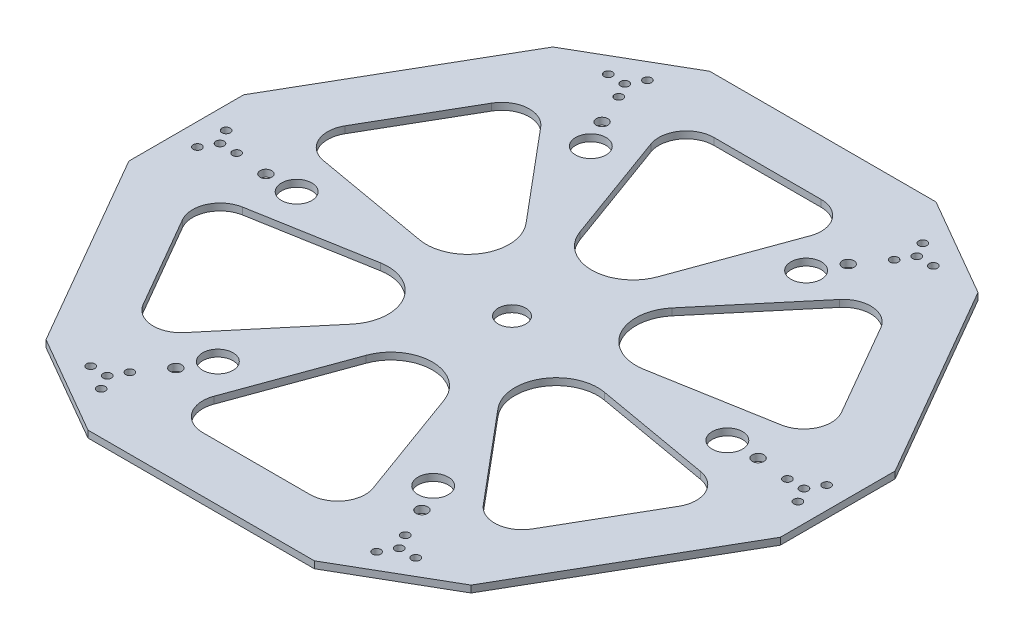
SolidWorks part; units mm, degrees
ref_plane "前视基准面" through (0, 0, 0) normal (0, 0, 1) x (1, 0, 0)
ref_plane "上视基准面" through (0, 0, 0) normal (0, 1, 0) x (1, 0, 0)
ref_plane "右视基准面" through (0, 0, 0) normal (1, 0, 0) x (0, 0, -1)
other "Configuration Table"
sketch "草图2" plane through (0, 0, 0) normal (0, 1, 0) x (1, 0, 0)
  line L1 (45, 0) -> (22.5, 38.9711)
  line L2 (22.5, 38.9711) -> (-22.5, 38.9711)
  line L3 (-22.5, 38.9711) -> (-45, 0)
  line L4 (-45, 0) -> (-22.5, -38.9711)
  line L5 (-22.5, -38.9711) -> (22.5, -38.9711)
  line L6 (22.5, -38.9711) -> (45, 0)
  line L7 (-54.5, 0) -> (-27.25, -47.1984)
  line L8 (-27.25, -47.1984) -> (27.25, -47.1984)
  line L9 (27.25, -47.1984) -> (54.5, 0)
  line L10 (54.5, 0) -> (27.25, 47.1984)
  line L11 (27.25, 47.1984) -> (-27.25, 47.1984)
  line L12 (-27.25, 47.1984) -> (-54.5, 0)
  circle A0 centre (0, 0) radius 38.9711 construction
  circle A1 centre (0, 0) radius 47.1984 construction
  circle A2 centre (0, 0) radius 5
  dimension "D3" = 10
  dimension "D1" = 45
  dimension "D2" = 9.5
extrude "凸台-拉伸1" add sketch "草图2" along normal blind 2.5 contours L5 L6 L1 L2 L3 L4 | L11 L12 L7 L8 L9 L10 L6 L5 L4 L3 L2 L1 region at (32.7189, 0, 18.8903) region at (-39.6262, 0, -22.8782)
sketch "草图3" plane through (0, 2.5, 0) normal (0, 1, 0) x (1, 0, 0)
  line L7 (-45, 0) -> (-22.5, -38.9711) construction
  line L8 (-22.5, -38.9711) -> (22.5, -38.9711) construction
  line L9 (22.5, -38.9711) -> (45, 0) construction
  line L10 (45, 0) -> (22.5, 38.9711) construction
  line L11 (22.5, 38.9711) -> (-22.5, 38.9711) construction
  line L12 (-22.5, 38.9711) -> (-45, 0) construction
  circle A0 centre (0, 0) radius 38.9711 construction
  circle A7 centre (-22.5, 38.9711) radius 2.1
  circle A8 centre (22.5, 38.9711) radius 2.1
  circle A9 centre (45, 0) radius 2.1
  circle A10 centre (22.5, -38.9711) radius 2.1
  circle A11 centre (-22.5, -38.9711) radius 2.1
  circle A12 centre (-45, 0) radius 2.1
  point P23 (0, 0)
  point P24 (0, 0)
  dimension "D2" = 4.2
  dimension "D1" = 45
  dimension "D3" = 6
extrude "切除-拉伸1" [suppressed] cut sketch "草图3" against normal blind 2.5
sketch "草图4" plane through (0, 2.5, 0) normal (0, 1, 0) x (1, 0, 0)
  line L0 (-27.25, 47.1984) -> (-54.5, 0) construction
  line L1 (-54.5, 0) -> (-27.25, -47.1984)
  line L2 (-27.25, -47.1984) -> (27.25, -47.1984)
  line L3 (27.25, -47.1984) -> (54.5, 0)
  line L4 (54.5, 0) -> (27.25, 47.1984)
  line L5 (27.25, 47.1984) -> (-27.25, 47.1984)
  line L6 (-27.25, 47.1984) -> (-54.5, 0)
  line L7 (-100.688, 0) -> (-50.344, -87.1984)
  line L8 (-50.344, -87.1984) -> (50.344, -87.1984)
  line L9 (50.344, -87.1984) -> (100.688, 0)
  line L10 (100.688, 0) -> (50.344, 87.1984)
  line L11 (50.344, 87.1984) -> (-50.344, 87.1984)
  line L12 (-50.344, 87.1984) -> (-100.688, 0)
  circle A0 centre (0, 0) radius 47.1984 construction
  circle A1 centre (0, 0) radius 87.1984 construction
  dimension "D1" = 40
extrude "凸台-拉伸2" add sketch "草图4" against normal up to surface (2.5 mm away) up to face at (0, 0, 5)
sketch "草图5" plane through (0, 2.5, 0) normal (0, 1, 0) x (1, 0, 0)
  line L0 (-50.344, 87.1984) -> (-100.688, 0) construction
  line L1 (-89.141, 0) -> (-44.5705, -77.1984) construction
  line L2 (-44.5705, -77.1984) -> (44.5705, -77.1984) construction
  line L3 (44.5705, -77.1984) -> (89.141, 0) construction
  line L4 (89.141, 0) -> (44.5705, 77.1984) construction
  line L5 (44.5705, 77.1984) -> (-44.5705, 77.1984) construction
  line L6 (-44.5705, 77.1984) -> (-89.141, 0) construction
  circle A0 centre (0, 0) radius 77.1984 construction
  circle A1 centre (-44.5705, 77.1984) radius 2.1
  circle A2 centre (44.5705, 77.1984) radius 2.1
  circle A3 centre (89.141, 0) radius 2.1
  circle A4 centre (44.5705, -77.1984) radius 2.1
  circle A5 centre (-44.5705, -77.1984) radius 2.1
  circle A6 centre (-89.141, 0) radius 2.1
  point P24 (0, 0)
  dimension "D2" = 4.2
  dimension "D1" = 10
  dimension "D3" = 6
extrude "切除-拉伸2" cut sketch "草图5" against normal blind 10
sketch "草图8" plane through (0, 2.5, 0) normal (0, 1, 0) x (1, 0, 0)
  line L0 (50.344, 87.1984) -> (-50.344, 87.1984) construction
  line L1 (-100.688, 0) -> (-50.344, -87.1984) construction
  circle A0 centre (-44.5705, 77.1984) radius 10
  circle A1 centre (44.5705, 77.1984) radius 10
  circle A2 centre (89.141, 0) radius 10
  circle A3 centre (44.5705, -77.1984) radius 10
  circle A4 centre (-44.5705, -77.1984) radius 10
  circle A5 centre (-89.141, 0) radius 10
  circle A6 centre (-113.6008, 65.5875) radius 60
  circle A7 centre (0, 131.175) radius 60
  circle A8 centre (113.6008, 65.5875) radius 60
  circle A9 centre (113.6008, -65.5875) radius 60
  circle A10 centre (0, -131.175) radius 60
  circle A11 centre (-113.6008, -65.5875) radius 60
  point P36 (0, 0)
  line M23 (-50.344, 87.1984) -> (-100.688, 0)
  line M24 (-100.688, 0) -> (-50.344, -87.1984)
  line M25 (-50.344, -87.1984) -> (50.344, -87.1984)
  line M26 (50.344, -87.1984) -> (100.688, 0)
  line M27 (100.688, 0) -> (50.344, 87.1984)
  line M28 (50.344, 87.1984) -> (-50.344, 87.1984)
  dimension "D1" = 120
  dimension "D2" = 6
extrude "切除-拉伸3" cut sketch "草图8" against normal blind 10 contours A0 M28 M23 | A7 A0 M28 | A6 A0 M23 | A7 M28 | A8 M27 | A9 M26 | A10 M25 | A11 M24 | A6 M23 | A1 M27 M28 | A7 A1 M28 | A8 A1 M27 | A8 A2 M27 | A2 M26 M27 | A9 A2 M26 | A9 A3 M26 | A10 A3 M25 | A3 M25 M26 | A11 A4 M24 | A4 M24 M25 | A10 A4 M25 | A5 M23 M24 | A6 A5 M23 | A11 A5 M24 | A6 region at (-41.0716, 2.5, -86.7224) region at (0, 2.5, -80.7095) region at (-54.568, 2.5, -78.9302) region at (-69.8965, 2.5, -40.3547) region at (-49.7383, 2.5, -86.1493) region at (41.0716, 2.5, -86.7224) region at (49.7383, 2.5, -86.1493) region at (54.568, 2.5, -78.9302) region at (69.8965, 2.5, -40.3547) region at (-95.6395, 2.5, -7.7922) region at (95.6395, 2.5, -7.7922) region at (-99.4766, 2.5, 0) region at (99.4766, 2.5, 0) region at (95.6395, 2.5, 7.7922) region at (69.8965, 2.5, 40.3547) region at (-95.6395, 2.5, 7.7922) region at (-69.8965, 2.5, 40.3547) region at (54.568, 2.5, 78.9302) region at (41.0716, 2.5, 86.7224) region at (0, 2.5, 80.7095) region at (-54.568, 2.5, 78.9302) region at (49.7383, 2.5, 86.1493) region at (-41.0716, 2.5, 86.7224) region at (-49.7383, 2.5, 86.1493)
sketch "草图10" plane through (0, 2.5, 0) normal (0, 1, 0) x (1, 0, 0)
  line L0 (-123, 12.1244) -> (-123, -12.1244)
  line L1 (-130, 0) -> (-65, -112.5833)
  line L2 (-65, -112.5833) -> (65, -112.5833)
  line L3 (65, -112.5833) -> (130, 0)
  line L4 (130, 0) -> (65, 112.5833)
  line L5 (65, 112.5833) -> (-65, 112.5833)
  line L6 (-65, 112.5833) -> (-130, 0)
  line L7 (-51, 112.5833) -> (-72, 100.4589)
  line L8 (72, 100.4589) -> (51, 112.5833)
  line L9 (123, -12.1244) -> (123, 12.1244)
  line L10 (51, -112.5833) -> (72, -100.4589)
  line L11 (-72, -100.4589) -> (-51, -112.5833)
  circle A0 centre (0, 0) radius 112.5833 construction
  arc A3 (-38.2033, 84.9093) -> (38.2033, 84.9093) centre (0, 131.175) ccw
  arc A5 (-38.2033, 84.9093) -> (38.2033, 84.9093) centre (0, 131.175) ccw
  arc A17 (-38.2033, 84.9093) -> (-54.432, 75.5397) centre (-44.5705, 77.1984) ccw
  arc A18 (-38.2033, 84.9093) -> (-54.432, 75.5397) centre (-44.5705, 77.1984) ccw
  arc A19 (-92.6353, 9.3696) -> (-54.432, 75.5397) centre (-113.6008, 65.5875) ccw
  arc A20 (-92.6353, 9.3696) -> (-54.432, 75.5397) centre (-113.6008, 65.5875) ccw
  arc A21 (-92.6353, 9.3696) -> (-92.6353, -9.3696) centre (-89.141, 0) ccw
  arc A22 (-92.6353, 9.3696) -> (-92.6353, -9.3696) centre (-89.141, 0) ccw
  arc A23 (-54.432, -75.5397) -> (-92.6353, -9.3696) centre (-113.6008, -65.5875) ccw
  arc A36 (-54.432, -75.5397) -> (-92.6353, -9.3696) centre (-113.6008, -65.5875) ccw
  arc A37 (-54.432, -75.5397) -> (-38.2033, -84.9093) centre (-44.5705, -77.1984) ccw
  arc A38 (-54.432, -75.5397) -> (-38.2033, -84.9093) centre (-44.5705, -77.1984) ccw
  arc A39 (38.2033, -84.9093) -> (-38.2033, -84.9093) centre (0, -131.175) ccw
  arc A40 (38.2033, -84.9093) -> (-38.2033, -84.9093) centre (0, -131.175) ccw
  arc A41 (38.2033, -84.9093) -> (54.432, -75.5397) centre (44.5705, -77.1984) ccw
  arc A42 (38.2033, -84.9093) -> (54.432, -75.5397) centre (44.5705, -77.1984) ccw
  arc A43 (92.6353, -9.3696) -> (54.432, -75.5397) centre (113.6008, -65.5875) ccw
  arc A44 (92.6353, -9.3696) -> (54.432, -75.5397) centre (113.6008, -65.5875) ccw
  arc A45 (92.6353, -9.3696) -> (92.6353, 9.3696) centre (89.141, 0) ccw
  arc A46 (92.6353, -9.3696) -> (92.6353, 9.3696) centre (89.141, 0) ccw
  arc A47 (54.432, 75.5397) -> (92.6353, 9.3696) centre (113.6008, 65.5875) ccw
  arc A48 (54.432, 75.5397) -> (92.6353, 9.3696) centre (113.6008, 65.5875) ccw
  arc A49 (54.432, 75.5397) -> (38.2033, 84.9093) centre (44.5705, 77.1984) ccw
  arc A50 (54.432, 75.5397) -> (38.2033, 84.9093) centre (44.5705, 77.1984) ccw
  point P47 (0, 0)
  arc M32 (38.2033, 84.9093) -> (-38.2033, 84.9093) centre (0, 131.175) cw
  arc M33 (-38.2033, 84.9093) -> (-54.432, 75.5397) centre (-44.5705, 77.1984) ccw
  arc M34 (-54.432, 75.5397) -> (-92.6353, 9.3696) centre (-113.6008, 65.5875) cw
  arc M35 (-92.6353, 9.3696) -> (-92.6353, -9.3696) centre (-89.141, 0) ccw
  arc M36 (-92.6353, -9.3696) -> (-54.432, -75.5397) centre (-113.6008, -65.5875) cw
  arc M37 (-54.432, -75.5397) -> (-38.2033, -84.9093) centre (-44.5705, -77.1984) ccw
  arc M38 (-38.2033, -84.9093) -> (38.2033, -84.9093) centre (0, -131.175) cw
  arc M39 (38.2033, -84.9093) -> (54.432, -75.5397) centre (44.5705, -77.1984) ccw
  arc M40 (54.432, -75.5397) -> (92.6353, -9.3696) centre (113.6008, -65.5875) cw
  arc M41 (92.6353, -9.3696) -> (92.6353, 9.3696) centre (89.141, 0) ccw
  arc M42 (92.6353, 9.3696) -> (54.432, 75.5397) centre (113.6008, 65.5875) cw
  arc M43 (54.432, 75.5397) -> (38.2033, 84.9093) centre (44.5705, 77.1984) ccw
  dimension "D2" = 130
  dimension "D3" = 7
  dimension "D1" = 0
  dimension "D4" = 6
extrude "凸台-拉伸3" add sketch "草图10" against normal up to surface (2.5 mm away) contours L1 L11 L2 L10 L3 L9 L4 L8 L5 L7 L6 L0 M32 M43 M42 M41 M40 M39 M38 M37 M36 M35 M34 M33 region at (-94.6119, 2.5, -54.6242) up to face at (-89.141, 0, 2.1)
sketch "草图11" plane through (0, 2.5, 0) normal (0, 1, 0) x (1, 0, 0)
  line L0 (-123, 12.1244) -> (-123, -12.1244) construction
  line L1 (-123, 1.2426) -> (-107, 1.2426) construction
  line L2 (-107, 1.2426) -> (-101, 1.2426) construction
  circle A0 centre (-107, 1.2426) radius 1.5
  circle A1 centre (-101, 1.2426) radius 1.5
  circle A2 centre (-110, -3.9536) radius 1.5
  circle A3 centre (-110, 6.4387) radius 1.5
  point P12 (-107, 1.2426)
  dimension "D1" = 3
  dimension "D2" = 16
  dimension "D3" = 6
  dimension "D4" = 3
extrude "切除-拉伸4" cut sketch "草图11" against normal through all
pattern_circular "阵列(圆周)1" count 6 over 360 about axis through (0, 2.5, 0) along (0, 1, 0) of "切除-拉伸4"
sketch "草图12" plane through (0, 2.5, 0) normal (0, 1, 0) x (1, 0, 0)
  line L0 (0, 0) -> (60.8571, 0) construction
  line L1 (-118, 68.1273) -> (-118, -68.1273)
  line L2 (-118, -68.1273) -> (0, -136.2547)
  line L3 (0, -136.2547) -> (118, -68.1273)
  line L4 (118, -68.1273) -> (118, 68.1273)
  line L5 (118, 68.1273) -> (0, 136.2547)
  line L6 (0, 136.2547) -> (-118, 68.1273)
  line L7 (-51, 112.5833) -> (-72, 100.4589) construction
  line L9 (-145.896, 84.2331) -> (-145.896, -84.2331)
  line L10 (-145.896, -84.2331) -> (0, -168.4662)
  line L11 (0, -168.4662) -> (145.896, -84.2331)
  line L12 (145.896, -84.2331) -> (145.896, 84.2331)
  line L13 (145.896, 84.2331) -> (0, 168.4662)
  line L14 (0, 168.4662) -> (-145.896, 84.2331)
  circle A0 centre (0, 0) radius 118 construction
  circle A1 centre (0, 0) radius 145.896 construction
  line M51 (-123, -12.1244) -> (-72, -100.4589)
  line M52 (-72, -100.4589) -> (-51, -112.5833)
  line M53 (-51, -112.5833) -> (51, -112.5833)
  line M54 (51, -112.5833) -> (72, -100.4589)
  line M55 (72, -100.4589) -> (123, -12.1244)
  line M56 (123, -12.1244) -> (123, 12.1244)
  line M57 (123, 12.1244) -> (72, 100.4589)
  line M58 (72, 100.4589) -> (51, 112.5833)
  line M59 (51, 112.5833) -> (-51, 112.5833)
  line M60 (-51, 112.5833) -> (-72, 100.4589)
  line M61 (-72, 100.4589) -> (-123, 12.1244)
  line M62 (-123, 12.1244) -> (-123, -12.1244)
  dimension "D1" = 5
extrude "切除-拉伸12" cut sketch "草图12" against normal up to surface (2.5 mm away) contours L13 L14 L9 L10 L11 L12 L6 L5 L4 L3 L2 L1 M59 M58 M57 M56 M55 M54 M53 M52 M51 M62 M61 M60 | L3 M53 M54 M55 | L2 M51 M52 M53 | L1 M61 M62 M51 | L6 M59 M60 M61 | L5 M57 M58 M59 | L4 M55 M56 M57 | L9 L10 L11 L12 L13 L14 | L1 L2 L3 L4 L5 L6 region at (-120.2807, 2.5, 0) region at (-60.1404, 2.5, -104.1661) region at (-60.1404, 2.5, 104.1661) region at (60.1404, 2.5, -104.1661) region at (60.1404, 2.5, 104.1661) region at (120.2807, 2.5, 0) region at (-70.7194, 2.5, -122.4896) up to face at (53.2771, 0, -92.7934)
sketch "草图13" plane through (0, 2.5, 0) normal (0, 1, 0) x (1, 0, 0)
  circle A0 centre (-78, 0) radius 5.5
  circle A2 centre (-39, 67.55) radius 5.5
  circle A3 centre (39, 67.55) radius 5.5
  circle A4 centre (78, 0) radius 5.5
  circle A5 centre (39, -67.55) radius 5.5
  circle A6 centre (-39, -67.55) radius 5.5
  point P16 (0, 0)
  dimension "D1" = 11
  dimension "D2" = 78
  dimension "D3" = 6
extrude "切除-拉伸13" cut sketch "草图13" against normal blind 10
sketch "草图14" plane through (0, 2.5, 0) normal (0, 1, 0) x (1, 0, 0)
  line L0 (-41, 112.5833) -> (0, 0)
  line L1 (0, 0) -> (41, 112.5833)
  line L2 (41, 112.5833) -> (-41, 112.5833)
  line L3 (-33.7165, 92.5833) -> (33.7165, 92.5833)
  line L4 (0, 112.5833) -> (0, 0) construction
  circle A0 centre (0, 43.8353) radius 15
  circle A1 centre (-19.4323, 82.5833) radius 10
  circle A2 centre (19.4323, 82.5833) radius 10
  dimension "D1" = 30
  dimension "D3" = 20
  dimension "D4" = 20
  dimension "D2" = 20
extrude "切除-拉伸14" cut sketch "草图14" against normal blind 10 contours A2 | L3 L4 A0 L1 A2 | L4 L3 A1 L0 A0 | A1 | L4 A0 | A0 L4 region at (-10.5334, 2.5, -69.9077) region at (-19.4323, 2.5, -82.5833) region at (10.5334, 2.5, -69.9077) region at (-6.3662, 2.5, -43.8353) region at (19.4323, 2.5, -82.5833) region at (6.3662, 2.5, -43.8353)
pattern_circular "阵列(圆周)2" count 6 over 360 about axis through (0, 2.5, 0) along (0, 1, 0) of "切除-拉伸14"
